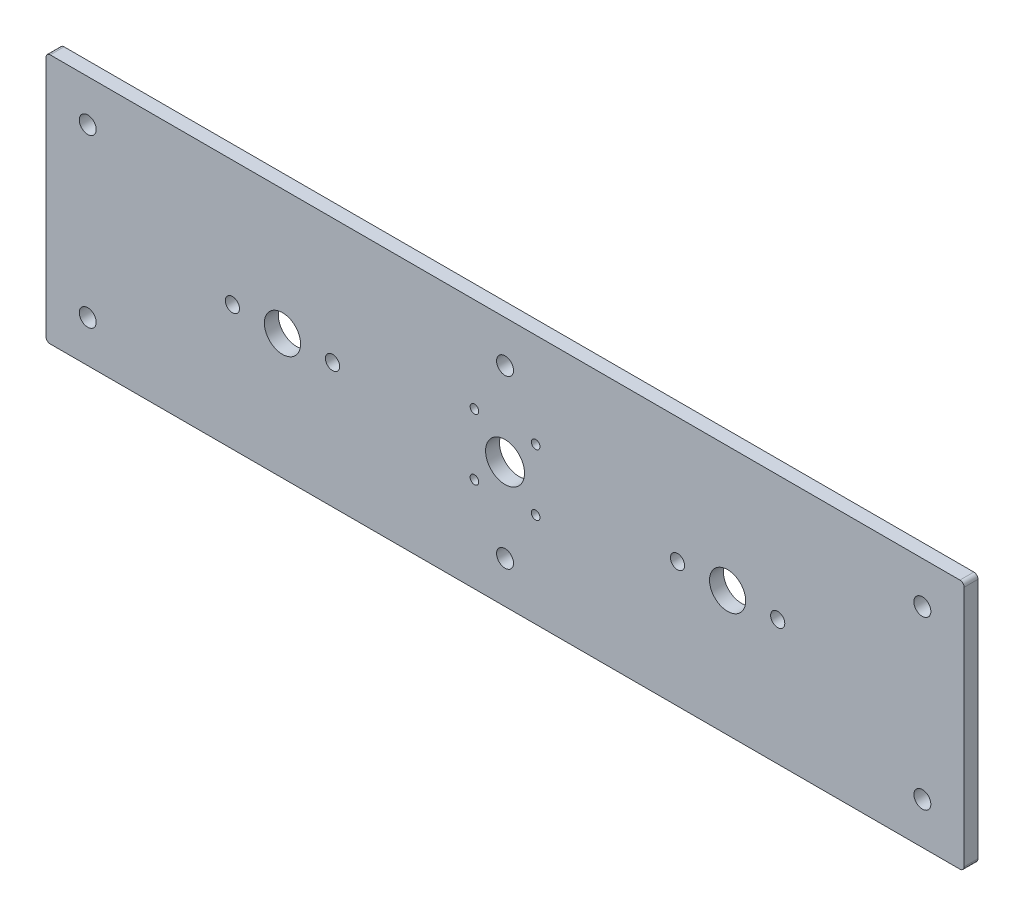
SolidWorks part; units mm, degrees
ref_plane "Front Plane" through (0, 0, 0) normal (0, 0, 1) x (1, 0, 0)
ref_plane "Top Plane" through (0, 0, 0) normal (0, 1, 0) x (1, 0, 0)
ref_plane "Right Plane" through (0, 0, 0) normal (1, 0, 0) x (0, 0, -1)
sketch "Sketch1" plane through (0, 0, 0) normal (0, 0, 1) x (1, 0, 0)
  line L1 (-165, -45) -> (165, -45)
  line L2 (-165, -45) -> (-165, 45)
  line L3 (-165, 45) -> (165, 45)
  line L4 (165, -45) -> (165, 45)
  line L5 (-165, -45) -> (165, 45) construction
  line L6 (-165, 45) -> (165, -45) construction
  point P0 (0, 0)
  dimension "D1" = 330
  dimension "D2" = 90
extrude "Boss-Extrude1" add sketch "Sketch1" along normal mid plane 5
sketch "Sketch2" plane through (0, 0, 2.5) normal (0, 0, 1) x (1, 0, 0)
  line L3 (165, 30) -> (-165, 30)
  line L4 (165, 30) -> (-165, 30) construction
  line L6 (-150, 45) -> (-150, -45)
  line L7 (-150, 45) -> (-150, -45) construction
  line L9 (-165, -30) -> (165, -30)
  line L10 (-165, -30) -> (165, -30) construction
  line L11 (0, 45) -> (0, -45) construction
  line L12 (150, -45) -> (150, 45)
  line L13 (150, -45) -> (150, 45) construction
  line L14 (165, 45) -> (-165, 45) construction
  line L15 (-165, -45) -> (165, -45) construction
  circle A0 centre (150, 30) radius 3.05
  circle A1 centre (150, -30) radius 3.05
  circle A2 centre (0, 30) radius 3.05
  circle A3 centre (0, -30) radius 3.05
  circle A4 centre (-150, -30) radius 3.05
  circle A5 centre (-150, 30) radius 3.05
  dimension "D5" = 6.1
  dimension "D6" = 6.1
  dimension "D7" = 6.1
  dimension "D8" = 6.1
  dimension "D9" = 6.1
  dimension "D10" = 6.1
  dimension "D1" = 15
  dimension "D2" = 15
  dimension "D3" = 15
  dimension "D4" = 15
extrude "Cut-Extrude1" cut sketch "Sketch2" against normal through all
sketch "Sketch3" plane through (0, 0, 2.5) normal (0, 0, 1) x (1, 0, 0)
  line L0 (-165, 0) -> (165, 0) construction
  line L1 (-165, 45) -> (-165, -45) construction
  line L2 (165, -45) -> (165, 45) construction
  circle A0 centre (-80, 0) radius 6.5
  circle A1 centre (-62, 0) radius 2.55
  circle A2 centre (-98, 0) radius 2.55
  dimension "D1" = 13
  dimension "D2" = 5.1
  dimension "D4" = 5.1
  dimension "D3" = 80
  dimension "D5" = 18
  dimension "D6" = 18
extrude "Cut-Extrude2" cut sketch "Sketch3" against normal through all
mirror "Mirror1" about plane through (0, 0, 0) normal (1, 0, 0) of "Cut-Extrude2"
sketch "Sketch4" plane through (0, 0, 2.5) normal (0, 0, 1) x (1, 0, 0)
  line L1 (-11, -11) -> (11, -11) construction
  line L2 (-11, -11) -> (-11, 11) construction
  line L3 (-11, 11) -> (11, 11) construction
  line L4 (11, -11) -> (11, 11) construction
  line L5 (-11, -11) -> (11, 11) construction
  line L6 (-11, 11) -> (11, -11) construction
  circle A0 centre (11, 11) radius 1.55
  circle A1 centre (11, -11) radius 1.55
  circle A2 centre (-11, -11) radius 1.55
  circle A3 centre (-11, 11) radius 1.55
  circle A4 centre (0, 0) radius 7
  point P0 (0, 0)
  dimension "D3" = 3.1
  dimension "D4" = 3.1
  dimension "D5" = 3.1
  dimension "D6" = 3.1
  dimension "D7" = 14
  dimension "D1" = 22
  dimension "D2" = 22
extrude "Cut-Extrude3" cut sketch "Sketch4" against normal through all
fillet "Fillet1" radius 1.5 4 edges at (-165, -45, 0) (-165, 45, 0) (165, -45, 0) (165, 45, 0)
equation "\"D3@Sketch3\"=160/2"
equation "\"D8@Sketch2\"=\"D5@Sketch2\""
equation "\"D9@Sketch2\"=\"D5@Sketch2\""
equation "\"D6@Sketch2\"=\"D5@Sketch2\""
equation "\"D7@Sketch2\"=\"D5@Sketch2\""
equation "\"D10@Sketch2\"=\"D5@Sketch2\""
